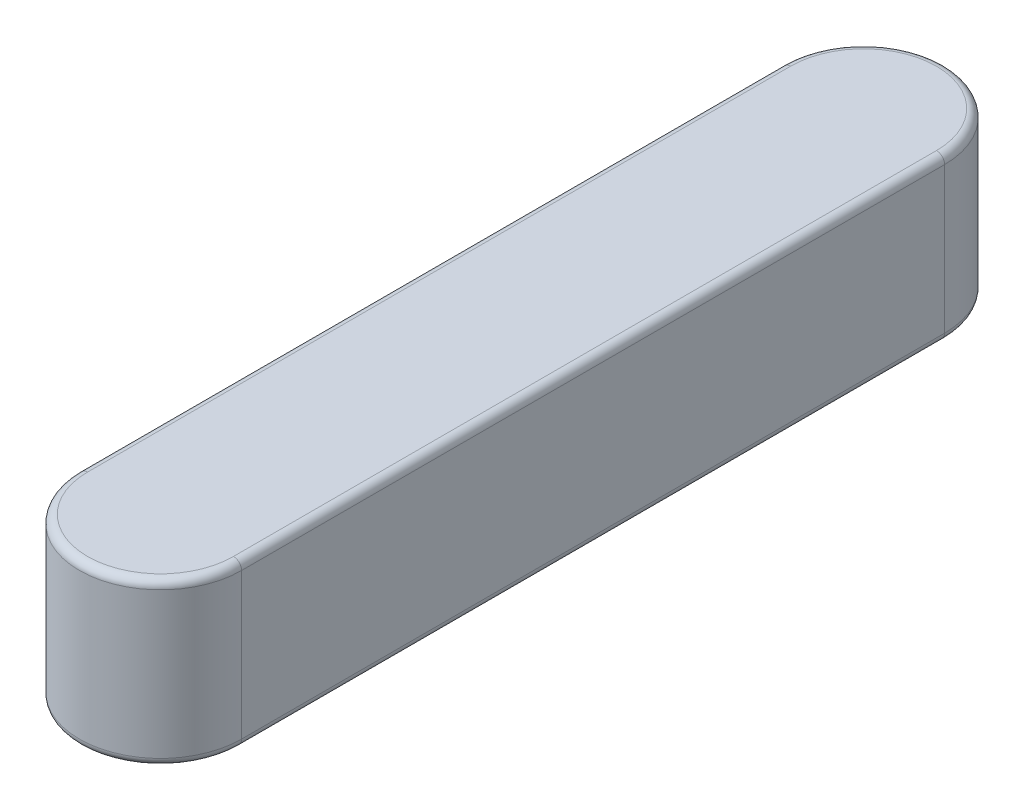
SolidWorks part; units mm, degrees
material "AISI 1045 Steel, cold drawn"
ref_plane "Front Plane" through (0, 0, 0) normal (0, 0, 1) x (1, 0, 0)
ref_plane "Top Plane" through (0, 0, 0) normal (0, 1, 0) x (1, 0, 0)
ref_plane "Right Plane" through (0, 0, 0) normal (1, 0, 0) x (0, 0, -1)
sketch "Sketch2" plane through (0, 0, 0) normal (1, 0, 0) x (0, 0, -1)
  line L0 (0, 2.3813) -> (0, -2.3813) construction
  line L1 (-12.7, -2.3813) -> (12.7, -2.3813)
  line L2 (-12.7, -2.3813) -> (-12.7, 2.3813)
  line L3 (-12.7, 2.3813) -> (12.7, 2.3813)
  line L4 (12.7, -2.3813) -> (12.7, 2.3813)
  line L5 (-12.7, -2.3813) -> (12.7, 2.3813) construction
  line L6 (-12.7, 2.3813) -> (12.7, -2.3813) construction
  line L7 (-12.7, 0) -> (12.7, 0) construction
  point P0 (0, 0)
  dimension "Length" = 25.4
  dimension "Height" = 4.7625
sketch "Sketch3" plane through (0, 0, 0) normal (0, 1, 0) x (1, 0, 0)
  line L0 (0, -12.7) -> (0, 12.7) construction
  line L5 (-2.3813, -12.7) -> (2.3812, -12.7)
  line L6 (-2.3813, -12.7) -> (-2.3813, 12.7)
  line L7 (-2.3813, 12.7) -> (2.3812, 12.7)
  line L8 (2.3812, -12.7) -> (2.3812, 12.7)
  line L9 (-2.3813, -12.7) -> (2.3812, 12.7) construction
  line L10 (-2.3813, 12.7) -> (2.3812, -12.7) construction
  point P0 (0, 0)
  dimension "Width" = 4.7625
sketch "Sketch4" plane through (0, 0, 0) normal (0, 1, 0) x (1, 0, 0)
  line L0 (0, -12.7) -> (0, 12.7) construction
  line L1 (-2.3812, 10.3187) -> (2.3812, 10.3187) construction
  line L2 (-2.3812, 10.3187) -> (-2.3813, -10.3187)
  line L3 (-2.3813, -10.3187) -> (2.3813, -10.3187) construction
  line L4 (2.3812, 10.3187) -> (2.3813, -10.3187)
  line L5 (2.3812, -12.7) -> (2.3812, 12.7) construction
  arc A0 (-2.3813, -10.3187) -> (2.3813, -10.3187) centre (0, -10.3187) ccw
  arc A1 (-2.3812, 10.3187) -> (2.3812, 10.3187) centre (0, 10.3187) cw
  point P4 (0, 10.3187)
  point P10 (0, 12.7)
  point P11 (0, -12.7)
extrude "Boss-Extrude1" add sketch "Sketch4" against normal up to vertex (2.3813 mm away) from vertex up to point (0, -2.3813, 0) starting at point (0, 2.3813, 0)
fillet "Fillet1" radius 0.2381 8 edges at (-2.3813, -2.3813, 0) (0, -2.3813, 12.7) (2.3813, -2.3813, 0) (0, -2.3813, -12.7) (2.3813, 2.3813, 0) (0, 2.3813, 12.7) (-2.3813, 2.3813, 0) (0, 2.3813, -12.7)
equation "\"D1@Fillet1\"=.05*\"Height@Sketch2\""
